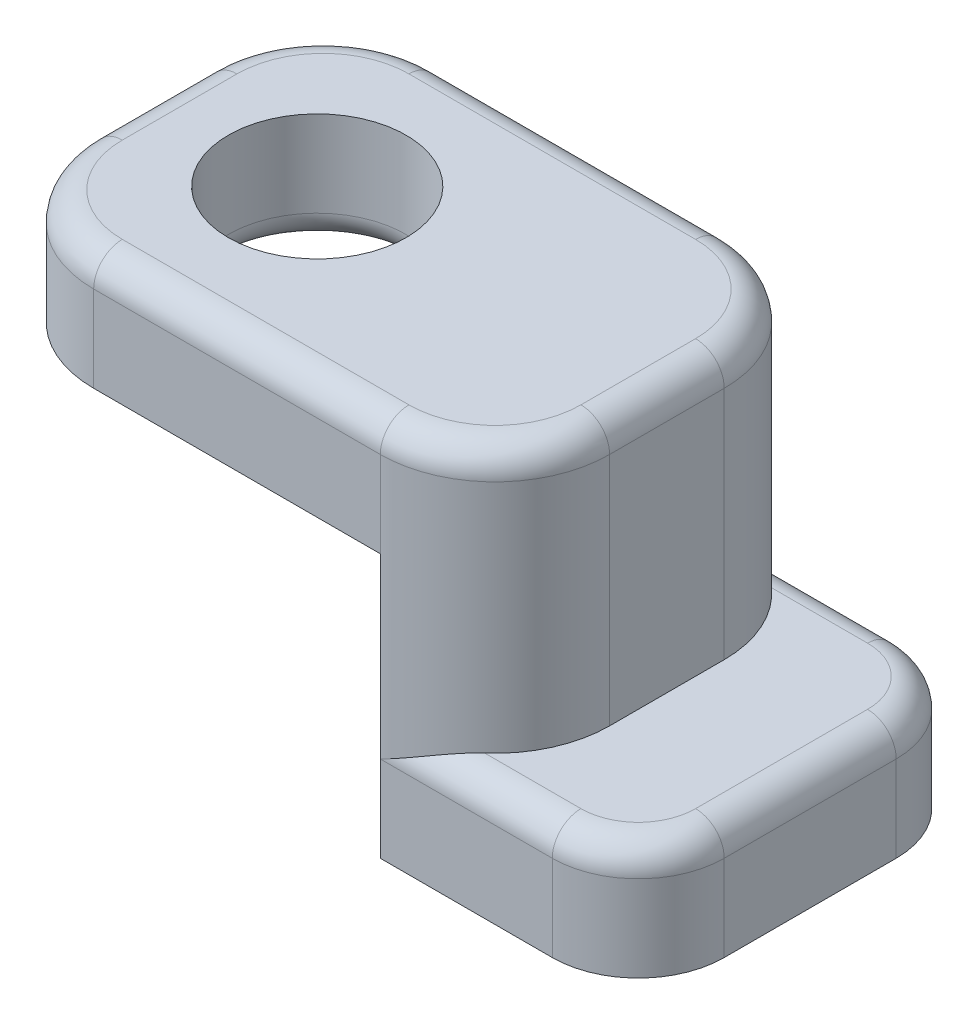
SolidWorks part; units mm, degrees
ref_plane "Front Plane" through (0, 0, 0) normal (0, 0, 1) x (1, 0, 0)
ref_plane "Top Plane" through (0, 0, 0) normal (0, 1, 0) x (1, 0, 0)
ref_plane "Right Plane" through (0, 0, 0) normal (1, 0, 0) x (0, 0, -1)
sketch "Sketch1" plane through (0, 0, 0) normal (0, 1, 0) x (1, 0, 0)
  line L1 (2.5, 3) -> (-2.5, 3)
  line L2 (4.5, 1) -> (4.5, -1)
  line L3 (2.5, -3) -> (-2.5, -3)
  line L4 (-4.5, 1) -> (-4.5, -1)
  line L5 (4.5, 3) -> (-4.5, -3) construction
  line L6 (4.5, -3) -> (-4.5, 3) construction
  arc A1 (-2.5, 3) -> (-4.5, 1) centre (-2.5, 1) ccw
  arc A2 (-2.5, -3) -> (-4.5, -1) centre (-2.5, -1) cw
  arc A3 (4.5, -1) -> (2.5, -3) centre (2.5, -1) cw
  arc A4 (2.5, 3) -> (4.5, 1) centre (2.5, 1) cw
  point P0 (0, 0)
  dimension "D1" = 2
  dimension "D2" = 9
  dimension "D3" = 6
extrude "Boss-Extrude1" add sketch "Sketch1" along normal blind 2
sketch "Sketch2" plane through (0, 2, 0) normal (0, 1, 0) x (1, 0, 0)
  line L0 (4.5, -1) -> (4.5, 1) construction
  line L2 (4.5, 0) -> (-4.5, 0) construction
  line L3 (-4.5, 1) -> (-4.5, -1) construction
  circle A0 centre (-1.6, 0) radius 1.55
  dimension "D1" = 3.1
  dimension "D2" = 6.1
extrude "Cut-Extrude1" cut sketch "Sketch2" against normal through all both and the other way through all
sketch "Sketch3" plane through (0, 0, 0) normal (0, -1, 0) x (1, 0, 0)
  line L1 (4.5, 1) -> (4.5, -1) construction
  line L4 (4.5, 1) -> (4.5, -1)
  line L6 (2.5, 3) -> (2.5, -3)
  arc A0 (2.5, -3) -> (4.5, -1) centre (2.5, -1) ccw construction
  arc A1 (4.5, 1) -> (2.5, 3) centre (2.5, 1) ccw construction
  arc A2 (2.5, -3) -> (4.5, -1) centre (2.5, -1) ccw
  arc A3 (4.5, 1) -> (2.5, 3) centre (2.5, 1) ccw
  dimension "D1" = 2
extrude "Boss-Extrude2" add sketch "Sketch3" along normal blind 4.6
sketch "Sketch4" plane through (0, -4.6, 0) normal (0, -1, 0) x (1, 0, 0)
  line L0 (4.5, 1) -> (4.5, -1) construction
  line L1 (4.5, 1) -> (4.5, -1)
  line L2 (2.5, 3) -> (5.5, 3)
  line L3 (7, 1.5) -> (7, -1.5)
  line L4 (5.5, -3) -> (2.5, -3)
  arc A0 (2.5, -3) -> (4.5, -1) centre (2.5, -1) ccw construction
  arc A1 (4.5, 1) -> (2.5, 3) centre (2.5, 1) ccw construction
  arc A2 (2.5, -3) -> (4.5, -1) centre (2.5, -1) ccw
  arc A3 (4.5, 1) -> (2.5, 3) centre (2.5, 1) ccw
  arc A4 (5.5, 3) -> (7, 1.5) centre (5.5, 1.5) cw
  arc A5 (7, -1.5) -> (5.5, -3) centre (5.5, -1.5) cw
  dimension "D1" = 1.5
  dimension "D2" = 2.5
extrude "Boss-Extrude3" add sketch "Sketch4" against normal blind 2
fillet "Fillet1" radius 0.5 14 edges at (3.9142, 2, 2.4142) (0, 2, 3) (-3.9142, 2, 2.4142) (-4.5, 2, 0) (-3.9142, 2, -2.4142) (0, 2, -3) (3.9142, 2, -2.4142) (4, -2.6, -3) (6.5607, -2.6, -2.5607) (4, -2.6, 3) (6.5607, -2.6, 2.5607) (-1.6, 0, 1.55) (4.5, 2, 0) (7, -2.6, 0)
